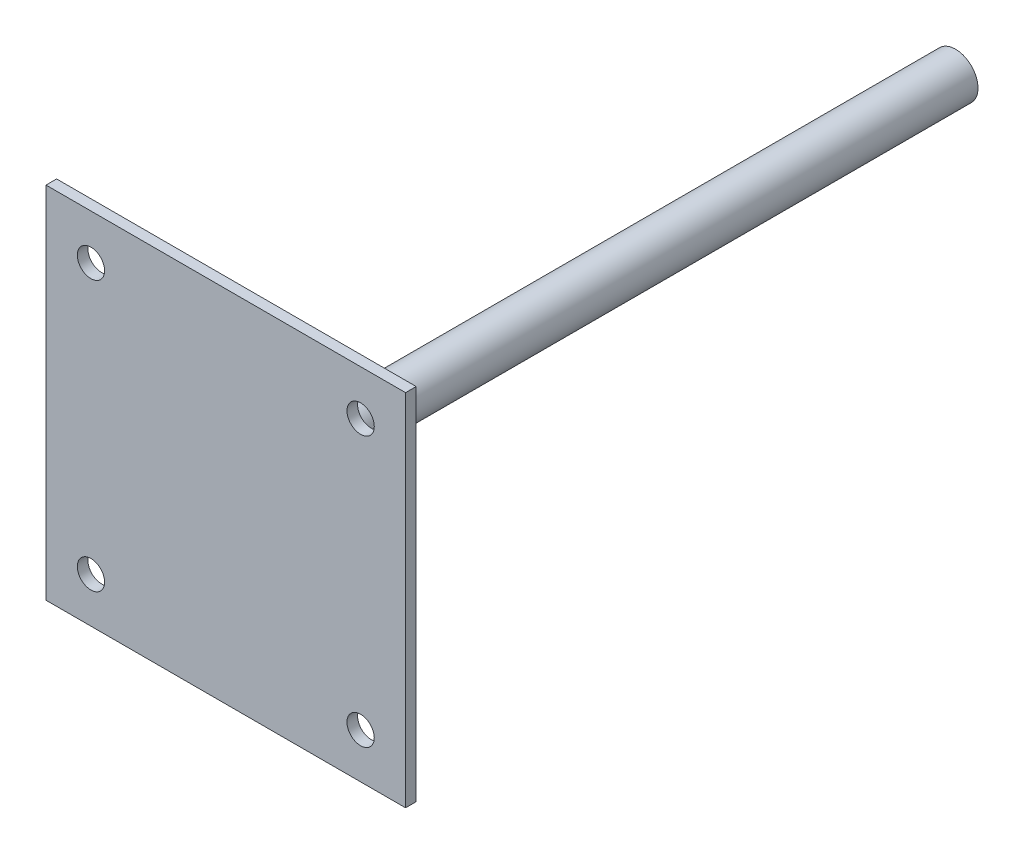
SolidWorks part; units mm, degrees
ref_plane "Front Plane" through (0, 0, 0) normal (0, 0, 1) x (1, 0, 0)
ref_plane "Top Plane" through (0, 0, 0) normal (0, 1, 0) x (1, 0, 0)
ref_plane "Right Plane" through (0, 0, 0) normal (1, 0, 0) x (0, 0, -1)
sketch "Sketch1" plane through (0, 0, 0) normal (0, 0, 1) x (1, 0, 0)
  line L0 (0, 50.8) -> (0, 0) construction
  line L1 (-50.8, 50.8) -> (50.8, 50.8)
  line L2 (-50.8, 50.8) -> (-50.8, -50.8)
  line L3 (-50.8, -50.8) -> (50.8, -50.8)
  line L4 (50.8, 50.8) -> (50.8, -50.8)
  line L5 (-50.8, 50.8) -> (50.8, -50.8) construction
  line L6 (-50.8, -50.8) -> (50.8, 50.8) construction
  line L7 (0, 0) -> (50.8, 0) construction
  circle A0 centre (0, 0) radius 6.35
  circle A1 centre (-38.1, 38.1) radius 3.8564
  circle A2 centre (38.1, 38.1) radius 3.8564
  circle A3 centre (38.1, -38.1) radius 3.8564
  circle A4 centre (-38.1, -38.1) radius 3.8564
  point P0 (0, 0)
  dimension "D1" = 12.7
  dimension "D2" = 12.7
  dimension "D3" = 12.7
  dimension "D4" = 50.8
extrude "Boss-Extrude1" add sketch "Sketch1" along normal blind 3 contours A0 | L4 L1 L2 L3 A2 A1 A0 A3 A4 region at (0, 49.3632, 0) region at (0, 0, 0)
extrude "Boss-Extrude2" add sketch "Sketch1<4>" against normal blind 203.2 contours A0 region at (0, 0, 0)
sketch "Sketch1<4>" plane through (0, 0, 0) normal (0, 0, 1) x (1, 0, 0) same geometry as "Sketch1"
